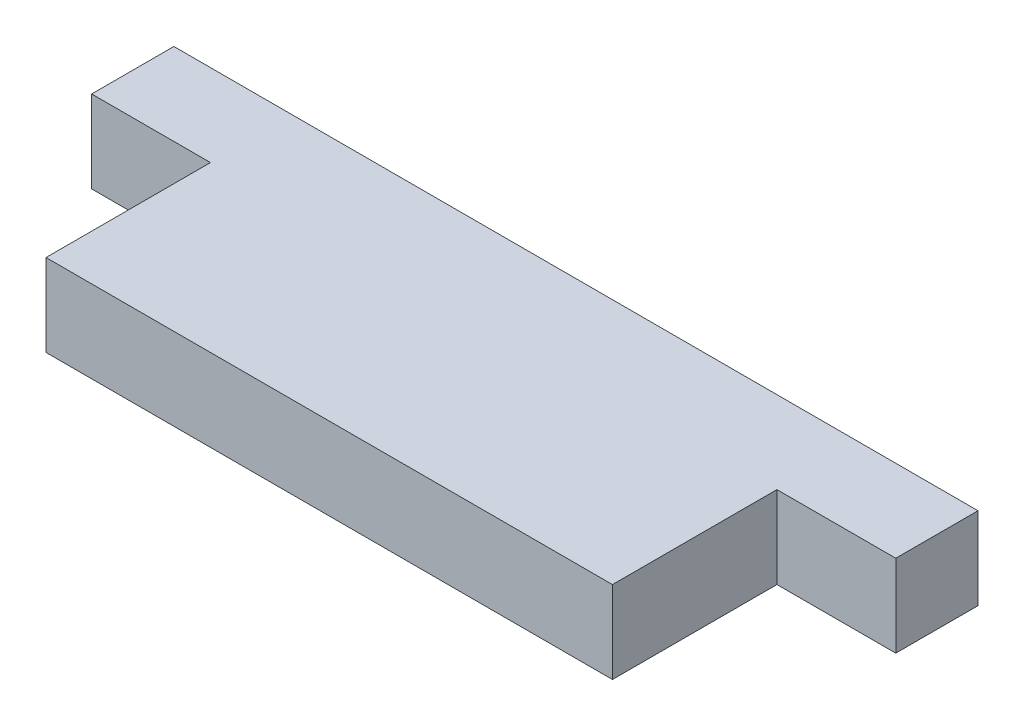
SolidWorks part; units mm, degrees
material "Beech"
ref_plane "Front Plane" through (0, 0, 0) normal (0, 0, 1) x (1, 0, 0)
ref_plane "Top Plane" through (0, 0, 0) normal (0, 1, 0) x (1, 0, 0)
ref_plane "Right Plane" through (0, 0, 0) normal (1, 0, 0) x (0, 0, -1)
sketch "Sketch1" plane through (0, 0, 0) normal (0, 1, 0) x (1, 0, 0)
  line L0 (0, 0) -> (0, 12.7)
  line L1 (0, 0) -> (43.74, 0)
  line L3 (43.74, 0) -> (43.74, 12.7)
  line L4 (-9.1751, 19.05) -> (52.9151, 19.05)
  line L5 (-9.1751, 19.05) -> (-9.1751, 12.7)
  line L6 (52.9151, 19.05) -> (52.9151, 12.7)
  line L7 (-9.1751, 12.7) -> (0, 12.7)
  line L8 (43.74, 12.7) -> (52.9151, 12.7)
  dimension "D1" = 12.7
  dimension "D2" = 43.74
  dimension "D3" = 6.35
  dimension "D4" = 9.1751
  dimension "D5" = 9.1751
extrude "Boss-Extrude1" add sketch "Sketch1" along normal blind 6.35
equation "\"MotorMountLegLength\"=.25in"
equation "\"GearOffset\"=.264907in"
equation "\"D4@Sketch1\"=\"TriggerRackOffset\"+.125in"
equation "\"D5@Sketch1\"=\"TriggerRackOffset\"+.125in"
equation "\"D2@Sketch1\" = \"CageLeftBottomEdge\" + \"CageRightBottomEdge\""
equation "\"CageLeftBottomEdge\"=22.11mm"
equation "\"CageLeftTopEdge\"=22.11mm"
equation "\"CageRightBottomEdge\"=21.63mm"
equation "\"CageRightTopEdge\"=21.63mm"
equation "\"CageHeight\"=86.04mm"
equation "\"CageLength\"=73.76mm"
equation "\"CageTopScrewClearance\"=10mm"
equation "\"CageBottomScrewClearance\"=25mm"
equation "\"CageLeftTopDepth\"= 11.65mm"
equation "\"CageLeftBottomDepth\"=11.11mm"
equation "\"CageLeftTopHeight\"=8.56175mm"
equation "\"CageLeftBottomHeight\"=16mm"
equation "\"CageRightTopDepth\"= 11.05mm"
equation "\"CageRightBottomDepth\"=10.58mm"
equation "\"CageRightTopHeight\"=9.6mm"
equation "\"CageRightBottomHeight\"=15.49mm"
equation "\"CageLeftTopChannelDepth\"=2.41908mm"
equation "\"CageLeftBottomChannelDepth\"=2.588mm"
equation "\"CageLeftChannelHeight\"=11.7mm"
equation "\"CageRightTopChannelDepth\"=2.32mm"
equation "\"CageRightBottomChannelDepth\"=2.318mm"
equation "\"CageRightChannelHeight\"=10mm"
equation "\"CageChanRelHeight\"=23.99mm"
equation "\"CageChanRelDepth\"=5.492mm"
equation "\"CageChamberRadius\"=16.261mm"
equation "\"CageScrewDiameter\"=4.8mm"
equation "\"CageSetScrewDiameter\"=3.5mm"
equation "\"CageAxleRadius\"=6.639mm"
equation "\"CageAxleKeyHeight\"=1.619mm"
equation "\"CageAxleKeyWidth\"=2.662mm"
equation "\"CageHoseWindowWidth\"=16.29mm"
equation "\"CageHoseWindowHeight\"=26.5mm"
equation "\"CageHoseWindow-Edge\"=8.89mm"
equation "\"CageScrew-VerticalEdge\"=5.0mm"
equation "\"CageScrew-HorizontalEdge\"=7.5mm"
equation "\"CageScrew-HoseCornerScrewEdge\"=4.45mm"
equation "\"CageAxle-BottomEdge\"=56.05mm"
equation "\"CageAxle-FrontEdge\"=46.03mm"
equation "\"CageBackSetScrew-Axle\"=40mm"
equation "\"CageFrontSetScrew-Axle\"=22mm"
equation "\"CageVelocityWindow-BackEdge\"=34.8mm"
equation "\"CageVelocityWindow-BottomEdge\"=27.55mm"
equation "\"CageVelocityWindowHeight\"=22.29mm"
equation "\"CageVelocityWindowWidth\"=12.61mm"
equation "\"TriggerSlot-BottomEdge\"=6.35mm"
equation "\"TriggerSlot-FrontEdge\"=15mm"
equation "\"TriggerSlotSize\"=6.7mm"
equation "\"TriggerRackOffset\"=.236224in"
equation "\"TriggerSlotSizeInt\"=.25in"
equation "\"TriggerSlotSpacing\"=.25in"
equation "\"TriggerMiniSlotWidth\"=3.5mm"
equation "\"TriggerRackWidth\"=6.5mm"
equation "\"TGMGearFaceDiameter\"=24.40mm"
equation "\"TGMCylinderLength\"=15.00mm"
equation "\"TGMScrewHole-Center\"=8.70mm"
equation "\"TGMScrewHoleDiameter\"=5.04mm"
equation "\"TGMCenterHoleDiameter\"=9.50mm"
equation "\"TGMShaftCollarSideLength\"=19.00mm"
equation "\"TGMShaftCollarDockingDepth\"=7.00mm"
equation "\"whitemotordepth\"=11.27mm"
equation "\"whitemotorbackdepth\"=3.845mm"
equation "\"whitemotoraxledepth\" = 3.5mm"
equation "\"whitemotoraxleoffset\"=11.4mm"
equation "\"whitemotorwidth\"=12.07mm"
equation "\"whitemotorheight\"=16.68mm"
equation "\"whitemotorcylinderlength\" =13.04mm"
equation "\"whitemotorcylinderradius\"=3.845mm"
equation "\"whitemotorcylinderoffset\"=2.35mm"
equation "\"whitemotorcutoutlength\"=1.88mm"
equation "\"whitemotorouterrad\"=5mm"
equation "\"whitemotorinnerrad\"=2.95mm"
equation "\"elasticracklength\"=2in"
equation "\"elasticrackpegsize\"=.25in"
equation "\"elasticrackpegbuffer\"=.125in"
equation "\"elasticrackpegspacing\"=1.76476378in"
equation "\"elasticbaybuffer\"=.25in"
equation "\"elasticdepth\"=.125in"
equation "\"elasticbaydepth\"=.75in"
equation "\"motormountwidth\"=12mm"
equation "\"motormountcornerfillet\"=3mm"
equation "\"pandiscradius\"=14in"
equation "\"towermaterialwidth\"=.25in"
equation "\"towerslotlength\"=.5in"
equation "\"towermarkerspace\"=5in"
equation "\"towerslothorizoffset\"=1in"
equation "\"towerslothorizspacing\"=2in"
equation "\"towerslotvertoffset\"=3in"
equation "\"towerslotvertspacing\"=2in"
equation "\"towerheight\"=12in"
equation "\"towerupslot\"=1in"
equation "\"toweraxle\"=.5in"
equation "\"towerplatslotoffset\"=1.5in"
equation "\"towermotorpanelheight\"=10in"
equation "\"towerplatdepth\"=2in"
equation "\"stepperouterrad\"=10mm"
equation "\"stepperscrewsize\"=3.45mm"
equation "\"stepperscrewc2c\"=49.5mm"
equation "\"stepperdepthoffset\"=24mm"
equation "\"stepperhorizoffset\"=22.91mm"
